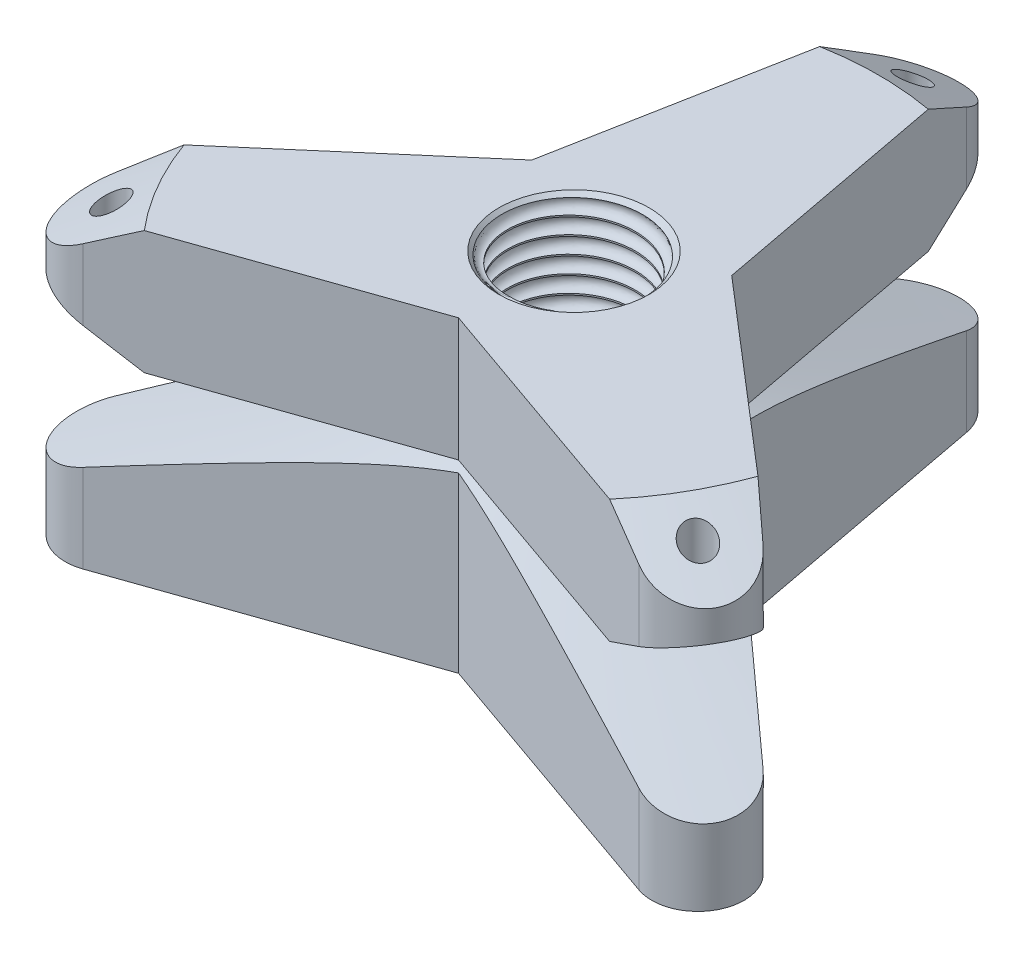
SolidWorks part; units mm, degrees
note: The reader was unsure of these and kept them because the rebuilt part matched: shared geometry of "Sketch1<10>".
ref_plane "Front Plane" through (0, 0, 0) normal (0, 0, 1) x (1, 0, 0)
ref_plane "Top Plane" through (0, 0, 0) normal (0, 1, 0) x (1, 0, 0)
ref_plane "Right Plane" through (0, 0, 0) normal (1, 0, 0) x (0, 0, -1)
sketch "Sketch1" plane through (0, 0, 0) normal (0, 1, 0) x (1, 0, 0)
  line L26 (0, 0) -> (0, 22) construction
  line L27 (0, 0) -> (0, 22) construction
  line L36 (0, 0) -> (-6.4952, 3.75) construction
  line L43 (-2.948, 22.5561) -> (-6.4952, 3.75)
  line L44 (2.948, 22.5561) -> (6.4952, 3.75)
  line L45 (21.0081, -8.725) -> (6.4952, 3.75)
  line L46 (18.0601, -13.8311) -> (0, -7.5)
  line L47 (-18.0601, -13.8311) -> (0, -7.5)
  line L48 (-21.0081, -8.725) -> (-6.4952, 3.75)
  circle A24 centre (0, 22) radius 1
  circle A53 centre (19.0526, -11) radius 1
  circle A54 centre (-19.0526, -11) radius 1
  circle A61 centre (0, 0) radius 4.15
  circle A70 centre (0, 0) radius 22 construction
  circle A85 centre (0, 0) radius 7.5 construction
  circle A86 centre (0, 0) radius 25 construction
  arc A92 (2.948, 22.5561) -> (-2.948, 22.5561) centre (0, 22) ccw
  arc A93 (18.0601, -13.8311) -> (21.0081, -8.725) centre (19.0526, -11) ccw
  arc A94 (-21.0081, -8.725) -> (-18.0601, -13.8311) centre (-19.0526, -11) ccw
  point P21 (0, 0)
  point P31 (0, 0)
  point P33 (0, 0)
  point P37 (0, 0)
  point P47 (0, 0)
  point P48 (0, 0)
  point P66 (0, 0)
  dimension "D1" = 8.3
  dimension "D2" = 15
  dimension "D3" = 44
  dimension "D4" = 3
  dimension "D5" = 50
  dimension "D6" = 2
  dimension "D7" = 60
extrude "Boss-Extrude1" add sketch "Sketch1" against normal blind 20
ref_plane "Plane4" through (0, -4, 0) normal (0, 1, 0) x (1, 0, 0)
sketch "Sketch54" plane through (0, 0, 0) normal (0, 1, 0) x (1, 0, 0)
  circle A0 centre (0, 0) radius 4.15 construction
  circle A1 centre (0, 0) radius 4.15
sketch "Sketch62" plane through (0, 0, 0) normal (0, 1, 0) x (1, 0, 0)
  circle A0 centre (0, 0) radius 4.8812
extrude "Cut-Extrude4" cut sketch "Sketch62" against normal blind 0.5 draft 45
sketch "Sketch74" plane through (0, 0, 0) normal (1, 0, 0) x (0, 0, -1)
  line L6 (0, 0) -> (0, -9.6234) construction
  line L7 (25, 0) -> (19.8038, 0)
  line L8 (22.5561, 0) -> (3.75, 0) construction
  line L9 (19.8038, 0) -> (25, -3)
  line L10 (25, -20) -> (25, 0) construction
  line L11 (25, -3) -> (25, 0)
  dimension "D1" = 3
  dimension "D2" = 60
revolve "Cut-Revolve1" cut sketch "Sketch74" angle 360 about L6
extrude "Cut-Extrude6" cut sketch "Sketch1<10>" against normal blind 10 contours A54 | A53 | A24
sketch "Sketch1<10>" plane through (0, 0, 0) normal (0, 1, 0) x (1, 0, 0) same geometry as "Sketch1"
mirror "Mirror1" about plane through (0, -4, 0) normal (0, 1, 0) of "Cut-Revolve1"
curve "Helix/Spiral2" pitch 1.1 height 7.7 turns 7
sweep "Cut-Sweep4" cut path "Helix/Spiral2" parameters "D3"=1
sketch "Sketch89" plane through (0, -20, 0) normal (0, -1, 0) x (1, 0, 0)
  circle A0 centre (0, 0) radius 4.15
curve "Helix/Spiral3" pitch 1.1 height 7.7 turns 7
sweep "Cut-Sweep5" cut path "Helix/Spiral3" circular profile diameter 1 parameters "D3"=1
sketch "Sketch95" plane through (0, 0, 0) normal (1, 0, 0) x (0, 0, -1)
  line L5 (25, -8) -> (5.5, -8)
  line L6 (5.5, -8) -> (25, -15.0974)
  line L7 (25, -20) -> (25, -8) construction
  line L8 (25, -15.0974) -> (25, -8)
  line L10 (0, 0) -> (0, -20) construction
  line L11 (-8.725, -20) -> (3.75, -20) construction
  dimension "D1" = 5.5
  dimension "D2" = 20
revolve "Cut-Revolve2" cut sketch "Sketch95" angle 360 about L10
ref_plane "Plane5" through (0, -10, 0) normal (0, 1, 0) x (1, 0, 0)
sketch "Sketch98" plane through (0, -10, 0) normal (0, 1, 0) x (1, 0, 0)
  circle A0 centre (0, 0) radius 5.0623
  circle A1 centre (0, 0) radius 2.5
  dimension "D1" = 5
extrude "Boss-Extrude2" add sketch "Sketch98" along normal mid plane 6
sketch "Sketch94" plane through (0, 0, 0) normal (1, 0, 0) x (0, 0, -1)
  line L0 (1.5, -10) -> (19.9694, -16.3066)
  line L2 (23, -6.1547) -> (23, -1.8453) construction
  line L3 (21, -0.6906) -> (21, -7.3094) construction
  line L4 (23, -6.1547) -> (23, -1.8453) construction
  line L5 (21, -0.6906) -> (21, -7.3094) construction
  line L6 (22, -18.783) -> (22, -13.5619) construction
  line L7 (22, -19.1457) -> (22, -20)
  line L8 (22.5561, -20) -> (3.75, -20) construction
  arc A0 (22, -19.1457) -> (19.9694, -16.3066) centre (19, -19.1457) ccw
  point P15 (22, -17)
  dimension "D2" = 3
  dimension "D1" = 3
  dimension "D3" = 1.5
sweep "Cut-Sweep6" cut path "Sketch94" circular profile diameter 3 parameters "D3"=3
pattern_circular "CirPattern1" count 3 over 360 about axis through (0, 0, 0) along (0, 1, 0) of "Cut-Sweep6"
mirror "Mirror2" about plane through (0, -10, 0) normal (0, 1, 0) of "Cut-Extrude4"
